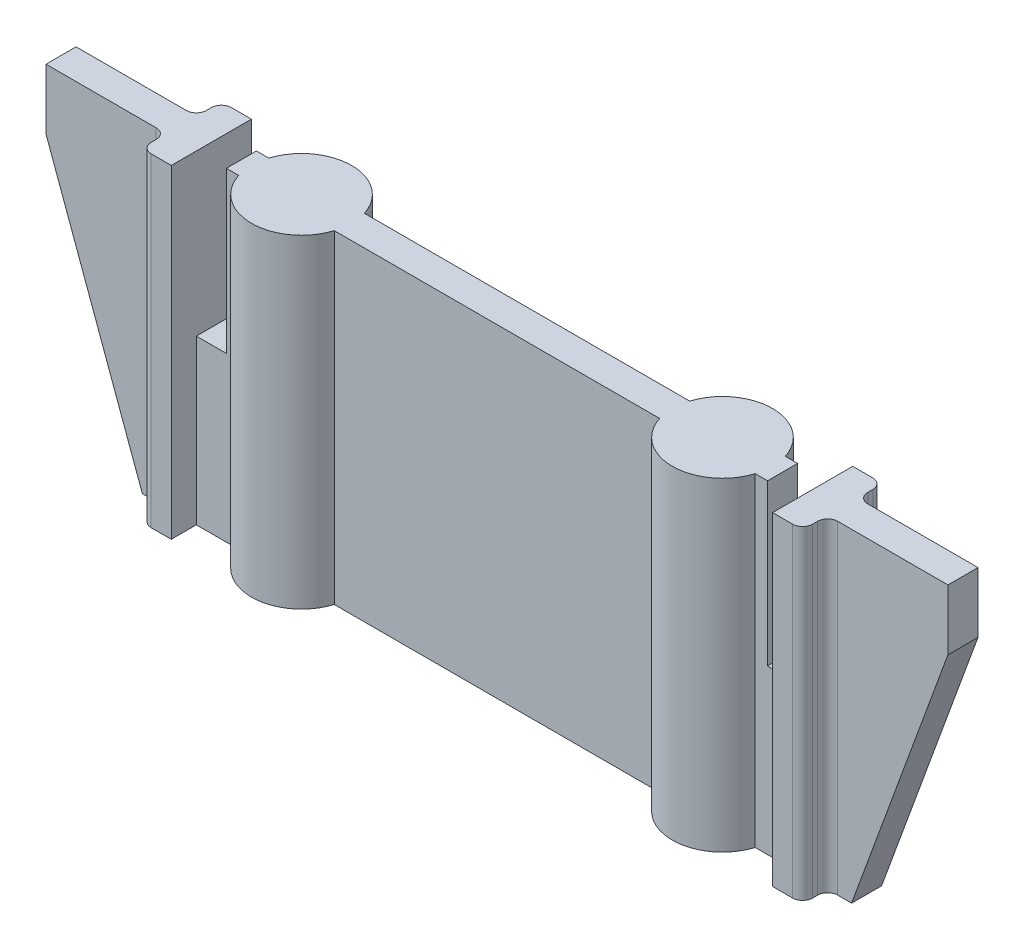
SolidWorks part; units mm, degrees
ref_plane "Front Plane" through (0, 0, 0) normal (0, 0, 1) x (1, 0, 0)
ref_plane "Top Plane" through (0, 0, 0) normal (0, 1, 0) x (1, 0, 0)
ref_plane "Right Plane" through (0, 0, 0) normal (1, 0, 0) x (0, 0, -1)
sketch "Sketch1" plane through (0, 0, 0) normal (0, 1, 0) x (1, 0, 0)
  line L0 (0, 0) -> (0, 10.4261) construction
  line L1 (-27, -17.5) -> (27, -17.5) construction
  line L2 (-27, -17.5) -> (-27, 11.1) construction
  line L3 (-27, 17.5) -> (27, 17.5) construction
  line L4 (27, -17.5) -> (27, 11.1) construction
  line L5 (-27, -17.5) -> (16.2, 10.5) construction
  line L6 (-27, 17.5) -> (-24.3041, 15.7527) construction
  line L7 (-27, 11.1) -> (-27, 12.9) construction
  line L8 (-45, 13.5) -> (-25.7697, 13.5)
  line L9 (-45, 13.5) -> (-45, 10.5)
  line L10 (-45, 10.5) -> (-25.7697, 10.5)
  line L11 (45, 13.5) -> (45, 10.5)
  line L12 (-45, 13.5) -> (-25.9248, 12.8642) construction
  line L13 (-45, 10.5) -> (-25.9248, 11.1358) construction
  line L14 (-27, 12.9) -> (-27, 17.5) construction
  line L15 (-19.5181, 12.6506) -> (-16.2252, 10.5163) construction
  line L16 (-17.6087, 11.413) -> (27, -17.5) construction
  line L17 (-16.0286, 12.5343) -> (0, 12) construction
  line L18 (17.6087, 11.413) -> (16.0286, 11.4657) construction
  line L19 (0, 12) -> (16.0286, 12.5343) construction
  line L20 (25.9248, 12.8642) -> (45, 13.5) construction
  line L21 (16.2252, 10.5163) -> (19.5181, 12.6506) construction
  line L22 (19.5181, 12.6506) -> (20.8286, 13.5) construction
  line L23 (16.0286, 11.4657) -> (25.9248, 11.1358) construction
  line L24 (25.9248, 11.1358) -> (45, 10.5) construction
  line L25 (16.2, 10.5) -> (17.6087, 11.413) construction
  line L26 (17.6087, 11.413) -> (16.2252, 10.5163) construction
  line L27 (0, 12) -> (17.6087, 11.413) construction
  line L28 (-16.2252, 10.5163) -> (-17.6087, 11.413) construction
  line L29 (-25.7697, 10.5) -> (-16.2303, 10.5) construction
  line L30 (-16.2303, 10.5) -> (16.2303, 10.5)
  line L31 (-25.9248, 11.1358) -> (-16.0286, 11.4657) construction
  line L32 (-16.0286, 11.4657) -> (0, 12) construction
  line L33 (-25.9248, 12.8642) -> (-19.5181, 12.6506) construction
  line L34 (-19.5181, 12.6506) -> (-16.0286, 12.5343) construction
  line L35 (-25.7697, 13.5) -> (-20.8286, 13.5) construction
  line L36 (-16.2303, 13.5) -> (16.2303, 13.5)
  line L37 (-24.3041, 15.7527) -> (-20.8286, 13.5) construction
  line L38 (-20.8286, 13.5) -> (-19.5181, 12.6506) construction
  line L39 (-20.8286, 13.5) -> (-16.2303, 13.5) construction
  line L40 (16.2303, 10.5) -> (10.6337, 10.5) construction
  line L41 (25.7697, 10.5) -> (45, 10.5)
  line L42 (16.0286, 12.5343) -> (19.5181, 12.6506) construction
  line L43 (16.2303, 13.5) -> (20.8286, 13.5) construction
  line L44 (25.7697, 13.5) -> (45, 13.5)
  line L45 (20.8286, 13.5) -> (24.3041, 15.7527) construction
  line L46 (24.3041, 15.7527) -> (27, 17.5) construction
  line L47 (20.8286, 13.5) -> (25.7697, 13.5) construction
  line L48 (19.5181, 12.6506) -> (45, 13.5) construction
  line L49 (27, 11.1) -> (27, 12.9) construction
  line L50 (27, 12.9) -> (27, 17.5) construction
  arc A0 (16.2252, 10.5163) -> (25.7697, 10.5) centre (21, 12) ccw construction
  arc A1 (-25.7697, 10.5) -> (-16.2303, 10.5) centre (-21, 12) ccw
  arc A2 (-25.9248, 12.8642) -> (-25.9248, 11.1358) centre (-21, 12) ccw construction
  arc A3 (-16.2252, 10.5163) -> (-16.0286, 11.4657) centre (-21, 12) ccw construction
  arc A4 (-16.2303, 13.5) -> (-25.7697, 13.5) centre (-21, 12) ccw
  arc A5 (16.0286, 12.5343) -> (16.2252, 10.5163) centre (21, 12) ccw construction
  arc A6 (16.2303, 13.5) -> (16.0286, 12.5343) centre (21, 12) ccw construction
  arc A7 (16.0286, 11.4657) -> (16.2303, 10.5) centre (21, 12) ccw construction
  arc A8 (16.2303, 10.5) -> (25.7697, 10.5) centre (21, 12) ccw
  arc A9 (-16.2303, 10.5) -> (-16.0286, 11.4657) centre (-21, 12) ccw construction
  arc A10 (-16.2303, 13.5) -> (-25.7697, 13.5) centre (-21, 12) ccw construction
  arc A11 (25.9248, 11.1358) -> (25.9248, 12.8642) centre (21, 12) ccw construction
  arc A12 (25.7697, 13.5) -> (16.2303, 13.5) centre (21, 12) ccw
  arc A13 (25.9248, 12.8642) -> (25.7697, 13.5) centre (21, 12) ccw construction
  arc A14 (25.7697, 10.5) -> (25.9248, 11.1358) centre (21, 12) ccw construction
  arc A15 (25.9248, 11.1358) -> (16.0286, 11.4657) centre (21, 12) ccw construction
  arc A16 (25.7697, 10.5) -> (25.9248, 11.1358) centre (21, 12) ccw construction
  arc A17 (-25.9248, 11.1358) -> (-25.7697, 10.5) centre (-21, 12) ccw construction
  arc A18 (-25.7697, 10.5) -> (-16.2252, 10.5163) centre (-21, 12) ccw construction
  arc A19 (-25.9248, 11.1358) -> (-25.7697, 10.5) centre (-21, 12) ccw construction
  arc A20 (-25.7697, 13.5) -> (-25.9248, 12.8642) centre (-21, 12) ccw construction
  arc A21 (-25.9248, 12.8642) -> (-25.9248, 11.1358) centre (-21, 12) ccw construction
  arc A22 (-25.7697, 13.5) -> (-25.9248, 12.8642) centre (-21, 12) ccw construction
  arc A23 (-16.0286, 11.4657) -> (-16.0286, 12.5343) centre (-21, 12) ccw construction
  arc A24 (-16.0286, 11.4657) -> (-16.0286, 12.5343) centre (-21, 12) ccw construction
  arc A25 (-16.0286, 12.5343) -> (-16.2303, 13.5) centre (-21, 12) ccw construction
  arc A26 (-16.0286, 12.5343) -> (-16.2303, 13.5) centre (-21, 12) ccw construction
  point P4 (0, 0)
  point P13 (0, 12)
  dimension "D1" = 10
  dimension "D2" = 3
  dimension "D3" = 54
  dimension "D4" = 35
  dimension "D5" = 42
  dimension "D6" = 90
  dimension "D7" = 12
extrude "Boss-Extrude1" add sketch "Sketch1" along normal blind 32.31 contours A4 L8 L9 L10 A1 L30 A8 L41 L11 L44 A12 L36
sketch "Sketch2" plane through (0, 0, -10.5) normal (0, 0, 1) x (1, 0, 0)
  line L0 (-35.3848, 0) -> (-45, 26.2724)
  line L1 (-45, 0) -> (-25.7697, 0) construction
  line L2 (-45, 32.31) -> (-45, 0) construction
  line L3 (-45, 26.2724) -> (-58.3904, 22.5254)
  line L4 (-58.3904, 22.5254) -> (-53.8147, -5.5007)
  line L5 (-53.8147, -5.5007) -> (-35.3848, -4.7634)
  line L6 (-35.3848, -4.7634) -> (-35.3848, 0)
  line L7 (0, 0) -> (0, 6.7705) construction
  line L8 (-16.2303, 0) -> (16.2303, 0) construction
  line L9 (53.8147, -5.5007) -> (35.3848, -4.7634)
  line L10 (58.3904, 22.5254) -> (53.8147, -5.5007)
  line L11 (45, 26.2724) -> (58.3904, 22.5254)
  line L12 (35.3848, 0) -> (45, 26.2724)
  line L13 (35.3848, -4.7634) -> (35.3848, 0)
extrude "Cut-Extrude1" cut sketch "Sketch2" against normal blind 25
sketch "Sketch3" plane through (0, 32.31, 0) normal (0, 1, 0) x (1, 0, 0)
  line L0 (0, 0) -> (0, 18.923) construction
  line L1 (-30, 3.9506) -> (-27, 3.9506)
  line L2 (-30, 3.9506) -> (-30, 20.1133)
  line L3 (-30, 20.1133) -> (-27, 20.1133)
  line L4 (-27, 3.9506) -> (-27, 20.1133)
  line L5 (-30, 3.9506) -> (-27, 20.1133) construction
  line L6 (-30, 20.1133) -> (-27, 3.9506) construction
  line L7 (30, 20.1133) -> (27, 20.1133)
  line L8 (27, 3.9506) -> (27, 20.1133)
  line L9 (30, 3.9506) -> (27, 3.9506)
  line L10 (30, 3.9506) -> (30, 20.1133)
  point P0 (-28.5, 12.032)
  dimension "D1" = 3
  dimension "D2" = 60
extrude "Cut-Extrude2" cut sketch "Sketch3" against normal blind 16
sketch "Sketch4" plane through (0, 0, 0) normal (0, -1, 0) x (1, 0, 0)
  line L1 (-33, -16) -> (-30, -16)
  line L2 (-33, -16) -> (-33, -8)
  line L3 (-33, -8) -> (-30, -8)
  line L4 (-30, -16) -> (-30, -8)
  line L5 (-33, -16) -> (-30, -8) construction
  line L6 (-33, -8) -> (-30, -16) construction
  line L7 (-35.3848, -12) -> (-14.4349, -12) construction
  line L8 (-35.3848, -10.5) -> (-35.3848, -13.5) construction
  line L9 (-30, -13.5) -> (-30, -10.5) construction
  point P0 (-31.5, -12)
  dimension "D1" = 3
  dimension "D2" = 8
extrude "Boss-Extrude2" add sketch "Sketch4" against normal up to surface (32.31 mm away) up to face at (-37.5, 32.31, -12)
fillet "Fillet1" radius 1 4 edges at (-33, 16.155, -16) (-33, 16.155, -8) (-33, 16.155, -10.5) (-33, 16.155, -13.5)
mirror "Mirror1" about plane through (0, 0, 0) normal (1, 0, 0) of "Boss-Extrude2"
fillet "Fillet2" radius 1 4 edges at (33, 16.155, -16) (33, 16.155, -13.5) (33, 16.155, -10.5) (33, 16.155, -8)
hole_wizard "M3 Clearance Hole1" positions "Sketch5" profile "Sketch6" hole size "M3" standard "ANSI Metric"
sketch "Sketch5" plane through (0, 0, 0) normal (0, -1, 0) x (-1, 0, 0)
  circle A0 centre (-21, 12) radius 5.6035 construction
  arc A1 (-16.2303, 13.5) -> (-25.7697, 13.5) centre (-21, 12) ccw construction
  arc A2 (25.7697, 13.5) -> (16.2303, 13.5) centre (21, 12) ccw construction
  point P0 (-21, 12)
  point P2 (21, 12)
sketch "Sketch6" plane through (21, 0, -12) normal (1, 0, 0) x (0, 0, -1)
  line L0 (0, 0) -> (0, 17.0815)
  line L1 (0, 17.0815) -> (1.8, 16)
  line L2 (1.8, 16) -> (1.8, 0)
  line L5 (1.8, 0) -> (0, 0)
  line L10 (0, 17.0815) -> (-1.8, 16) construction
  line L11 (0, -6.35) -> (0, 107.95) construction
  dimension "Hole Dia." = 3.6
  dimension "Hole Depth" = 16
  dimension "Drill Angle" = 118
ref_plane "Plane1" through (0, 10, 0) normal (0, -1, 0) x (-1, 0, 0)
sketch "Sketch7" plane through (0, 10, 0) normal (0, -1, 0) x (-1, 0, 0)
  line L1 (-21, 15.6373) -> (-24.15, 13.8187) construction
  line L2 (-24.15, 13.8187) -> (-24.15, 10.1813)
  line L3 (-24.15, 10.1813) -> (-21, 8.3627)
  line L4 (-21, 8.3627) -> (-17.85, 10.1813)
  line L5 (-17.85, 10.1813) -> (-17.85, 13.8187)
  line L6 (-17.85, 13.8187) -> (-21, 15.6373) construction
  line L7 (-24.15, 13.8187) -> (-17.85, 13.8187) construction
  line L8 (-24.15, 13.8187) -> (-24.15, 20.1574)
  line L9 (-24.15, 20.1574) -> (-17.85, 20.1574)
  line L10 (-17.85, 13.8187) -> (-17.85, 20.1574)
  circle A0 centre (-21, 12) radius 3.15 construction
  dimension "D1" = 6.3
extrude "Cut-Extrude3" cut sketch "Sketch7" along normal blind 4
mirror "Mirror2" about plane through (0, 0, 0) normal (1, 0, 0) of "Cut-Extrude3"
